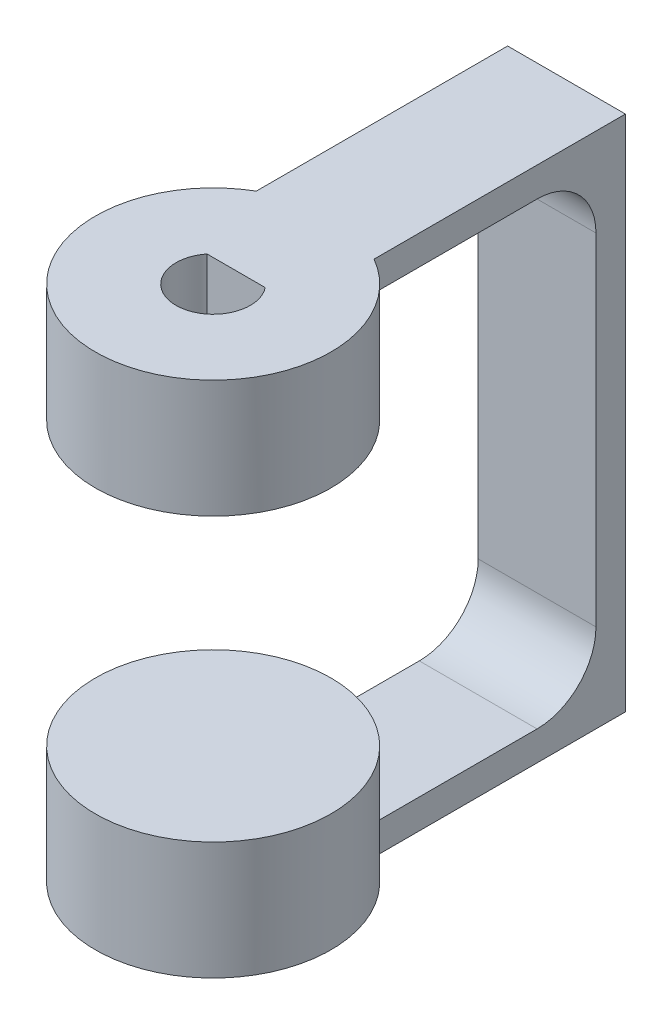
SolidWorks part; units mm, degrees
ref_plane "Front Plane" through (0, 0, 0) normal (0, 0, 1) x (1, 0, 0)
ref_plane "Top Plane" through (0, 0, 0) normal (0, 1, 0) x (1, 0, 0)
ref_plane "Right Plane" through (0, 0, 0) normal (1, 0, 0) x (0, 0, -1)
sketch "Sketch1" plane through (0, 0, 0) normal (0, 1, 0) x (1, 0, 0)
  circle A0 centre (0, 0) radius 12.7
  dimension "D1" = 25.4
extrude "Boss-Extrude1" add sketch "Sketch1" along normal mid plane 55.8292
sketch "Sketch4" plane through (0, 0, 0) normal (0, 0, 1) x (1, 0, 0)
  line L0 (-24.5861, 0) -> (49.9861, 0) construction
  line L1 (-12.7, 27.9146) -> (-12.7, -27.9146) construction
  line L2 (-12.7, 15.2146) -> (12.7, 15.2146)
  line L3 (-12.7, 15.2146) -> (-12.7, -15.2146)
  line L4 (-12.7, -15.2146) -> (12.7, -15.2146)
  line L5 (12.7, 15.2146) -> (12.7, -15.2146)
  point P7 (12.7, 0)
  point P8 (0, 15.2146)
  dimension "D1" = 30.4292
extrude "Cut-Extrude2" cut sketch "Sketch4" against normal through all both and the other way through all
sketch "Sketch5" plane through (0, 0, 0) normal (1, 0, 0) x (0, 0, -1)
  line L0 (-21.6052, 0) -> (34.6887, 0) construction
  line L1 (0, 27.9146) -> (38.1, 27.9146)
  line L2 (38.1, 27.9146) -> (38.1, -27.9146)
  line L4 (34.925, -24.7396) -> (34.925, 24.7396)
  line L5 (34.925, 24.7396) -> (0, 24.7396)
  line L6 (0, 24.7396) -> (0, 27.9146)
  line L7 (12.7, 27.9146) -> (-12.7, 27.9146) construction
  line L8 (0, -27.9146) -> (38.1, -27.9146)
  line L9 (34.925, -24.7396) -> (0, -24.7396)
  line L10 (0, -24.7396) -> (0, -27.9146)
  point P12 (34.925, 0)
  point P13 (38.1, 0)
  dimension "D1" = 3.175
  dimension "D2" = 3.175
  dimension "D3" = 38.1
extrude "Boss-Extrude2" add sketch "Sketch5" along normal mid plane 12.7
sketch "Sketch2" plane through (0, 27.9146, 0) normal (0, 1, 0) x (1, 0, 0)
  line L0 (-3.1408, 2.477) -> (3.1408, 2.477)
  arc A0 (-3.1408, 2.477) -> (3.1408, 2.477) centre (0, 0) ccw
  point P5 (0, -4)
  dimension "D1" = 8
  dimension "D2" = 6.477
extrude "Cut-Extrude3" cut sketch "Sketch2" against normal blind 10.16
mirror "Mirror1" about plane through (0, 0, 0) normal (0, 1, 0) of "Cut-Extrude3"
fillet "Fillet1" radius 6.35 2 edges at (0, -24.7396, -34.925) (0, 24.7396, -34.925)
